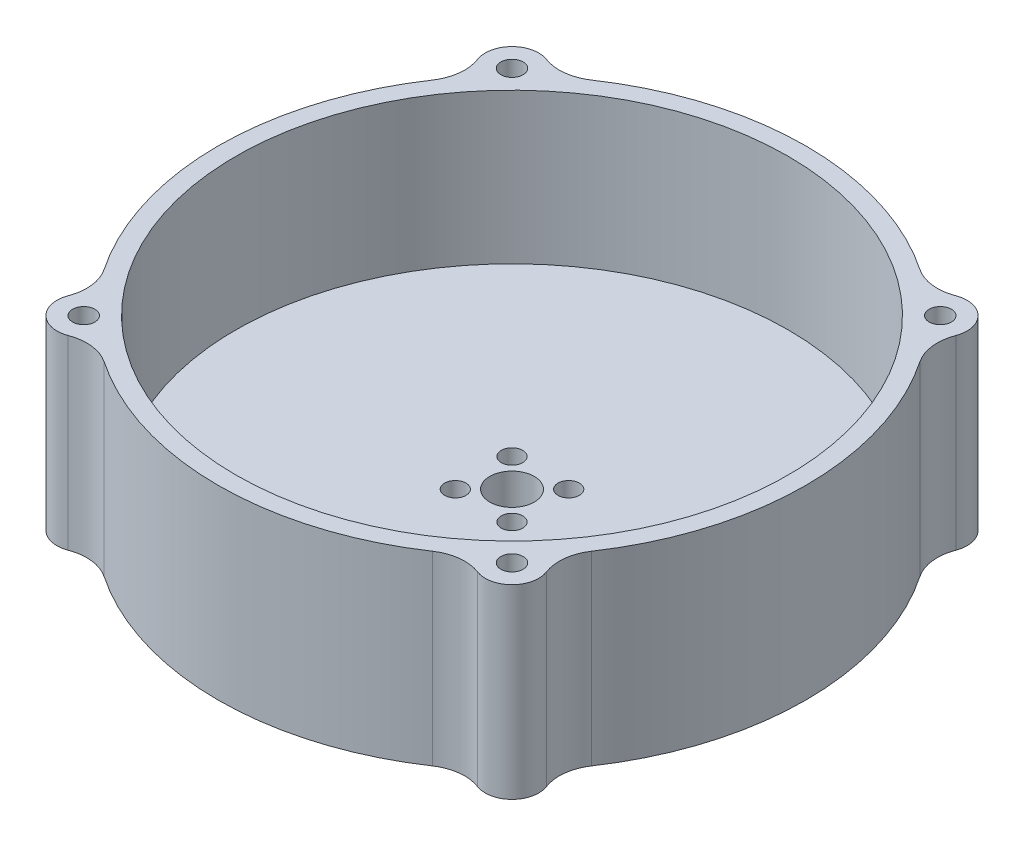
SolidWorks part; units mm, degrees
ref_plane "Front Plane" through (0, 0, 0) normal (0, 0, 1) x (1, 0, 0)
ref_plane "Top Plane" through (0, 0, 0) normal (0, 1, 0) x (1, 0, 0)
ref_plane "Right Plane" through (0, 0, 0) normal (1, 0, 0) x (0, 0, -1)
sketch "Sketch1" plane through (0, 0, 0) normal (0, 1, 0) x (1, 0, 0)
  circle A0 centre (0, 0) radius 33
  dimension "D1" = 66
extrude "Boss-Extrude1" add sketch "Sketch1" along normal blind 4
sketch "Sketch2" plane through (0, 4, 0) normal (0, 1, 0) x (1, 0, 0)
  circle A0 centre (0, 0) radius 31
  circle A1 centre (0, 0) radius 33 construction
  circle A2 centre (0, 0) radius 33
  dimension "D1" = 62
extrude "Boss-Extrude2" add sketch "Sketch2" along normal blind 16.88
sketch "Sketch5" plane through (0, 0, 0) normal (0, -1, 0) x (1, 0, 0)
  line L1 (-3.182, 3.182) -> (3.182, 3.182)
  line L2 (-3.182, 3.182) -> (-3.182, -3.182)
  line L3 (-3.182, -3.182) -> (3.182, -3.182)
  line L4 (3.182, 3.182) -> (3.182, -3.182)
  circle A0 centre (0, 0) radius 4.5
  dimension "D1" = 9
hole_wizard "M2 Clearance Hole1" positions "Sketch6" profile "Sketch8" hole size "M2" standard "ANSI Metric" end condition through all
sketch "Sketch6" plane through (0, 0, 0) normal (0, -1, 0) x (-1, 0, 0)
  point P0 (3.182, 3.182)
  point P3 (3.182, -3.182)
  point P6 (-3.182, -3.182)
  point P9 (-3.182, 3.182)
sketch "Sketch8" plane through (-3.182, 0, -3.182) normal (1, 0, 0) x (0, 0, -1)
  line L0 (0, 0) -> (0, 20.88)
  line L1 (0, 20.88) -> (1.2, 20.88)
  line L2 (1.2, 20.88) -> (1.2, 0)
  line L5 (1.2, 0) -> (0, 0)
  line L11 (0, -6.35) -> (0, 107.95) construction
  dimension "Thru Hole Dia." = 2.4
  dimension "Thru Hole Depth" = 20.88
sketch "Sketch13" plane through (0, 4, 0) normal (0, 1, 0) x (1, 0, 0)
  circle A0 centre (0, 0) radius 2.5
  dimension "D1" = 5
extrude "Cut-Extrude3" cut sketch "Sketch13" against normal through all
sketch "Sketch10" plane through (0, 4, 0) normal (0, 1, 0) x (1, 0, 0)
  line L0 (15, -4) -> (15, 4) construction
  line L1 (13.5, -4) -> (13.5, 4)
  line L2 (16.5, -4) -> (16.5, 4)
  arc A1 (13.5, -4) -> (16.5, -4) centre (15, -4) ccw
  arc A2 (16.5, 4) -> (13.5, 4) centre (15, 4) ccw
  point P2 (15, 0)
  dimension "D1" = 15
  dimension "D2" = 8
  dimension "D3" = 3
extrude "Cut-Extrude2" cut sketch "Sketch10" against normal through all
sketch "Sketch15" plane through (0, 20.88, 0) normal (0, 1, 0) x (1, 0, 0)
  line L0 (0, 0) -> (24.0416, 24.0416) construction
  line L1 (13.5, 4) -> (13.5, -4) construction
  circle A0 centre (24.0416, 24.0416) radius 3
  circle A1 centre (0, 0) radius 31 construction
  dimension "D1" = 6
  dimension "D2" = 45
extrude "Boss-Extrude3" add sketch "Sketch15" against normal through all
fillet "Fillet1" radius 5 2 edges at (21.2827, 10.44, -25.2199) (25.2199, 10.44, -21.2827)
pattern_circular "CirPattern1" count 4 over 360 about axis through (0, 4, 0) along (0, -1, 0) of "Boss-Extrude3", "Fillet1"
hole_wizard "M3x0.5 Tapped Hole1" positions "Sketch18" profile "Sketch19" tap size "M3x0.5" standard "ANSI Metric"
sketch "Sketch18" plane through (0, 20.88, 0) normal (0, 1, 0) x (1, 0, 0)
  point P5 (24.0416, -24.0416)
  point P8 (-24.0416, -24.0416)
  point P14 (-24.0416, 24.0416)
  point P17 (24.0416, 24.0416)
sketch "Sketch19" plane through (24.0416, 20.88, 24.0416) normal (1, 0, 0) x (0, 0, 1)
  line L0 (0, 0) -> (0, 8.2511)
  line L1 (0, 8.2511) -> (1.25, 7.5)
  line L2 (1.25, 7.5) -> (1.25, 0)
  line L5 (1.25, 0) -> (0, 0)
  line L10 (0, 8.2511) -> (-1.25, 7.5) construction
  line L11 (0, -6.35) -> (0, 107.95) construction
  dimension "Tap Drill Dia." = 2.5
  dimension "Tap Drill Depth" = 7.5
  dimension "Drill Angle" = 118
cosmetic thread "Hole Thread1" parameters "D1"=6, "D2"=3
cosmetic thread "Hole Thread2" parameters "D1"=6, "D2"=3
cosmetic thread "Hole Thread3" parameters "D1"=6, "D2"=3
cosmetic thread "Hole Thread4" parameters "D1"=6, "D2"=3
